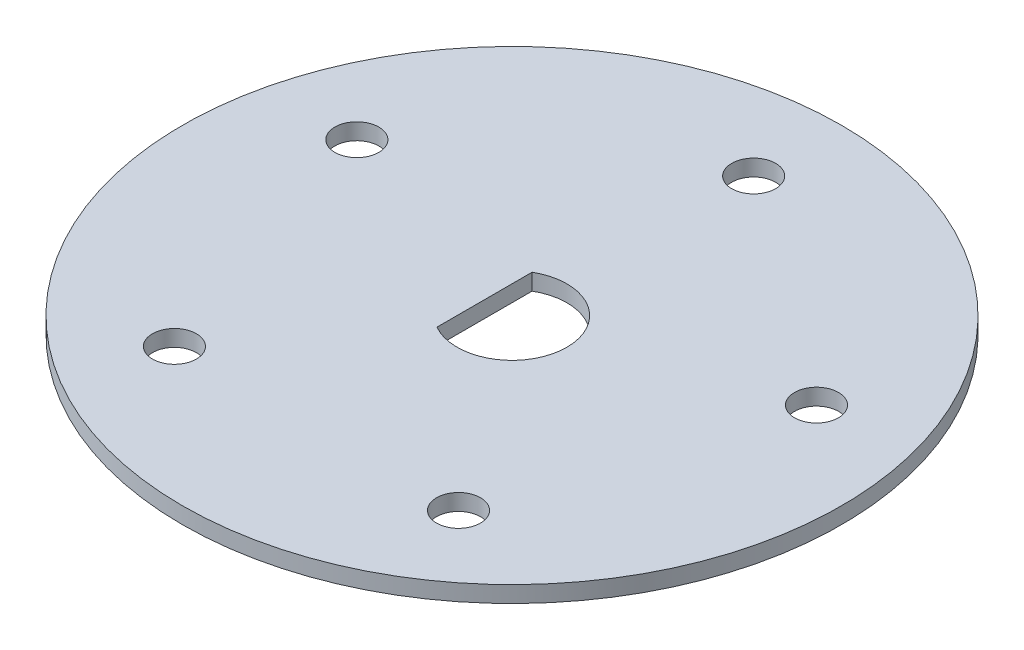
SolidWorks part; units mm, degrees
ref_plane "Front Plane" through (0, 0, 0) normal (0, 0, 1) x (1, 0, 0)
ref_plane "Top Plane" through (0, 0, 0) normal (0, 1, 0) x (1, 0, 0)
ref_plane "Right Plane" through (0, 0, 0) normal (1, 0, 0) x (0, 0, -1)
sketch "Sketch1" plane through (0, 0, 0) normal (0, 1, 0) x (1, 0, 0)
  line L2 (-3.175, 5.4993) -> (-3.175, -5.4993)
  circle A0 centre (0, 0) radius 38.1
  circle A2 centre (0, 27.94) radius 2.54
  circle A9 centre (26.5725, 8.6339) radius 2.54
  circle A10 centre (16.4227, -22.6039) radius 2.54
  circle A11 centre (-16.4227, -22.6039) radius 2.54
  circle A12 centre (-26.5725, 8.6339) radius 2.54
  arc A13 (-3.175, -5.4993) -> (-3.175, 5.4993) centre (0, 0) ccw
  point P18 (0, 0)
  point P19 (0, 0)
  dimension "D1" = 76.2
  dimension "D2" = 12.7
  dimension "D3" = 5.08
  dimension "D6" = 3.175
  dimension "D4" = 27.94
  dimension "D5" = 5
extrude "Boss-Extrude1" add sketch "Sketch1" along normal blind 1.8974 contours A0 | A12 | A11 | A10 | A9 | A13 L2 | A2
